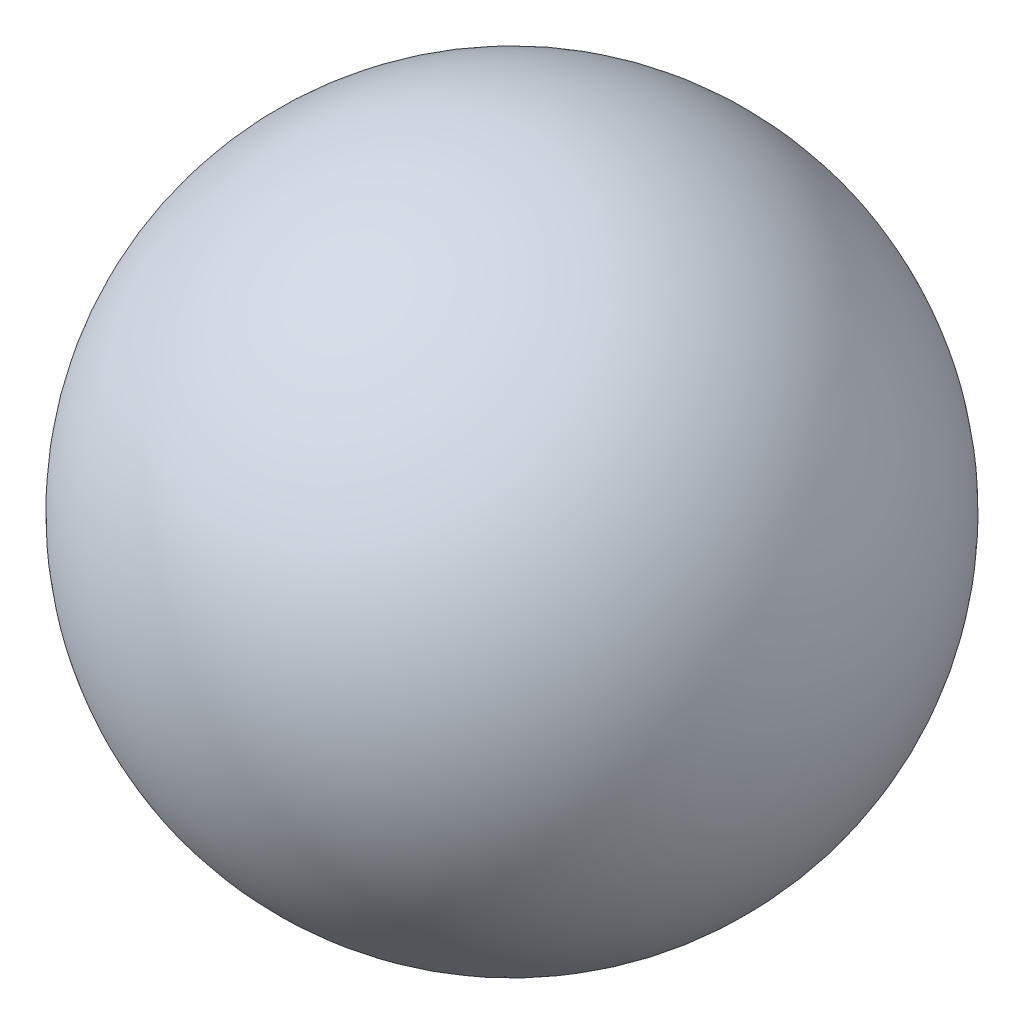
SolidWorks part; units mm, degrees
ref_plane "Front Plane" through (0, 0, 0) normal (0, 0, 1) x (1, 0, 0)
ref_plane "Top Plane" through (0, 0, 0) normal (0, 1, 0) x (1, 0, 0)
ref_plane "Right Plane" through (0, 0, 0) normal (1, 0, 0) x (0, 0, -1)
sketch "Sketch1" plane through (0, 0, 0) normal (0, 1, 0) x (1, 0, 0)
  line L0 (0, 44.45) -> (0, -44.45)
  arc A0 (0, 44.45) -> (0, -44.45) centre (0, 0) ccw
  arc A1 (0, 42.45) -> (0, -42.45) centre (0, 0) ccw
  dimension "D1" = 88.9
  dimension "D2" = 2
revolve "HollowBall" add sketch "Sketch1" angle 360 about L0 region at (-0.9939, 0, -43.45)
sketch "Heading" plane through (0, 0, 0) normal (0, 1, 0) x (1, 0, 0)
  line L0 (0, 0) -> (0, 44.45) construction
  line L1 (0, 0) -> (22.225, 38.4948) construction
  line L2 (0, 0) -> (38.4948, 22.225) construction
  line L3 (0, 0) -> (44.45, 0) construction
  line L4 (0, 0) -> (38.4948, -22.225) construction
  line L5 (0, 0) -> (22.225, -38.4948) construction
  line L6 (0, 0) -> (0, -44.45) construction
  line L7 (0, 0) -> (-22.225, -38.4948) construction
  line L8 (0, 0) -> (-38.4948, -22.225) construction
  line L9 (0, 0) -> (-44.45, 0) construction
  line L10 (0, 0) -> (-38.4948, 22.225) construction
  line L11 (0, 0) -> (-22.225, 38.4948) construction
  line L12 (0, 0) -> (0, 44.45) construction
  line L13 (0, 0) -> (22.225, 38.4948) construction
  circle A1 centre (0, 0) radius 44.45 construction
  dimension "D1" = 88.9
  dimension "D3" = 30
  dimension "D2" = 12
sketch "Pitch" plane through (0, 0, 0) normal (1, 0, 0) x (0, 0, -1)
  line L0 (0, 0) -> (44.45, 0) construction
  line L1 (0, 0) -> (38.4948, -22.225) construction
  line L2 (0, 0) -> (22.225, -38.4948) construction
  line L3 (0, 0) -> (0, -44.45) construction
  line L4 (0, 0) -> (-22.225, -38.4948) construction
  line L5 (0, 0) -> (-38.4948, -22.225) construction
  line L6 (0, 0) -> (-44.45, 0) construction
  line L7 (0, 0) -> (-38.4948, 22.225) construction
  line L8 (0, 0) -> (-22.225, 38.4948) construction
  line L9 (0, 0) -> (0, 44.45) construction
  line L10 (0, 0) -> (22.225, 38.4948) construction
  line L11 (0, 0) -> (38.4948, 22.225) construction
  line L12 (0, 0) -> (44.45, 0) construction
  line L13 (0, 0) -> (38.4948, -22.225) construction
  circle A0 centre (0, 0) radius 44.45 construction
  dimension "D1" = 88.9
  dimension "D3" = 30
  dimension "D2" = 12
ref_axis "Axis1" through (0, 0, 0) along (0, 1, 0)
ref_plane "Plane1" through (0, 38.4948, -22.225) normal (0, 0.866, -0.5) x (1, 0, 0)
sketch "Sketch4" plane through (0, 38.4948, -22.225) normal (0, 0.866, -0.5) x (1, 0, 0)
  line L0 (-1.861, 1.861) -> (-1.861, 12.3386)
  line L1 (-1.861, 12.3386) -> (1.861, 12.3386)
  line L2 (1.861, 12.3386) -> (1.861, 1.861)
  line L3 (1.861, 1.861) -> (12.3386, 1.861)
  line L4 (12.3386, 1.861) -> (12.3386, -1.861)
  line L5 (12.3386, -1.861) -> (1.861, -1.861)
  line L6 (1.861, -1.861) -> (1.861, -12.3386)
  line L7 (1.861, -12.3386) -> (-1.861, -12.3386)
  line L8 (-1.861, -12.3386) -> (-1.861, -1.861)
  line L9 (-1.861, -1.861) -> (-12.3386, -1.861)
  line L10 (-12.3386, -1.861) -> (-12.3386, 1.861)
  line L11 (-12.3386, 1.861) -> (-1.861, 1.861)
  point P2 (-12.3386, 0)
  point P13 (0, 12.3386)
  point P15 (-12.3386, 1.861)
